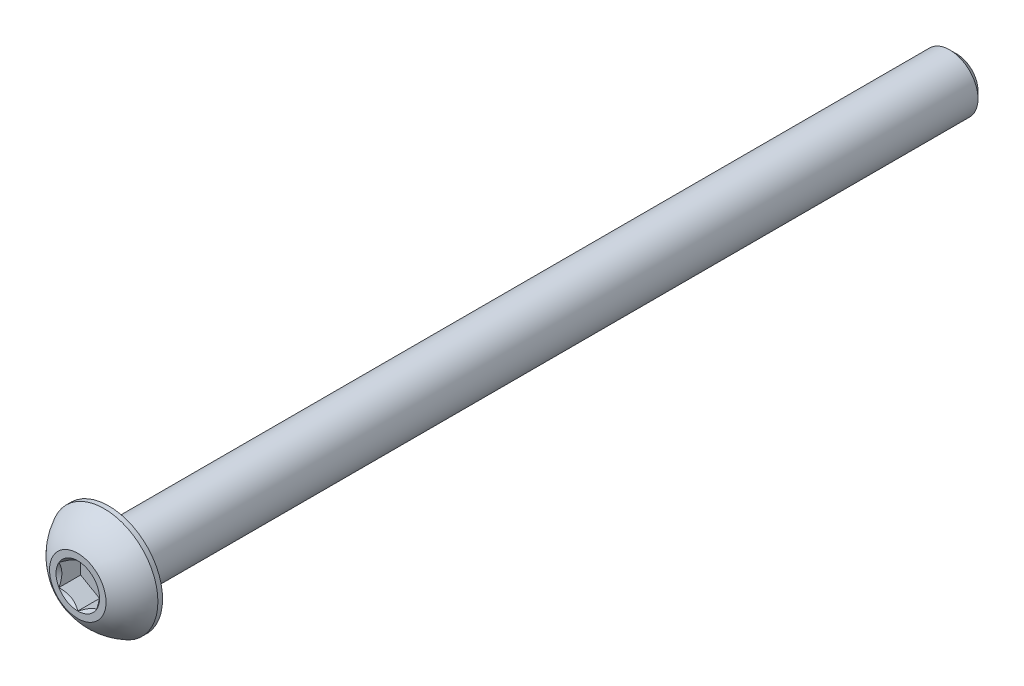
SolidWorks part; units mm, degrees
material "Chrome Stainless Steel"
ref_plane "Front" through (0, 0, 0) normal (0, 0, 1) x (1, 0, 0)
ref_plane "Top" through (0, 0, 0) normal (0, 1, 0) x (1, 0, 0)
ref_plane "Right" through (0, 0, 0) normal (1, 0, 0) x (0, 0, -1)
sketch "Sketch1" plane through (0, 0, 0) normal (1, 0, 0) x (0, 0, -1)
  line L2 (1.65, 1.5) -> (46.65, 1.5)
  line L3 (46.65, 1.5) -> (46.65, 0)
  line L4 (46.65, 0) -> (1.65, 0)
  line L6 (1.4025, 2.85) -> (1.65, 2.85) construction
  line L7 (46.65, 1.5) -> (46.65, -1.5) construction
  line L8 (0, 0) -> (1.65, 0) construction
  line L9 (1.65, 2.85) -> (1.65, -2.85) construction
  line L11 (1.65, 1.5) -> (1.65, 0)
  line L13 (0, 1) -> (0, -1) construction
  line L14 (0, 1) -> (0, 1.5) construction
  line L15 (46.6187, 1.5541) -> (46.8687, 1.1211) construction
  line L16 (46.8687, 1.1211) -> (47.1187, 1.5541) construction
  line L17 (47.1187, 1.5541) -> (46.6187, 1.5541) construction
  line L18 (46.65, 1.5) -> (47.0875, 1.5) construction
  line L19 (46.8687, 1.5541) -> (46.8687, 1.5) construction
  line L20 (46.8687, 1.5) -> (46.8687, 1.1752) construction
  line L21 (46.8687, 1.1752) -> (46.8687, 1.1211) construction
  line L22 (46.8375, 1.1752) -> (46.9, 1.1752)
  line L23 (46.6344, 1.5271) -> (47.1031, 1.5271)
  line L24 (46.9, 1.1752) -> (47.1031, 1.5271)
  line L25 (46.8375, 1.1752) -> (46.6344, 1.5271)
  line L26 (46.275, 1.5) -> (46.65, 1.125)
  arc A3 (0, 1.5) -> (1.4025, 2.85) centre (2.7948, 0) cw construction
  point P29 (46.8687, 1.5271)
  point P30 (45.4, -1.5)
  dimension "D1" = 0.2475
  dimension "Pitch" = 0.5
  dimension "D3" = 0.0625
  dimension "D2" = 0.375
  dimension "D4" = 45
  dimension "D5" = 1.25
sketch "Sketch10" plane through (0, 0, 0) normal (1, 0, 0) x (0, 0, -1)
  line L0 (46.275, 1.5) -> (46.65, 1.125) construction
  line L1 (46.275, 1.5) -> (46.65, 1.125)
  line L4 (46.65, 1.5) -> (1.65, 1.5)
  line L5 (46.65, 0) -> (46.65, 1.5)
  line L6 (1.65, 0) -> (46.65, 0)
  line L7 (1.65, 1.5) -> (1.65, 0)
  line L8 (46.275, 1.5) -> (1.65, 1.5)
  line L9 (46.65, 0) -> (46.65, 1.125)
  line L10 (1.65, 0) -> (46.65, 0)
  line L11 (1.65, 1.5) -> (1.65, 0)
  dimension "D1" = 0
revolve "Revolve3" add sketch "Sketch10" angle 360 about L8
sketch "Sketch7" plane through (0, 0, 0) normal (1, 0, 0) x (0, 0, -1)
  line L6 (1.4025, 2.85) -> (1.65, 2.85) construction
  line L8 (0, 0) -> (1.65, 0) construction
  line L11 (1.65, 2.85) -> (1.65, -2.85) construction
  line L12 (1.4025, 2.85) -> (1.65, 2.85)
  line L13 (0, 0) -> (1.65, 0)
  line L14 (0, 1) -> (0, -1) construction
  line L15 (1.65, 2.85) -> (1.65, 0)
  line L16 (0, 1.5) -> (0, 0)
  arc A2 (1.4025, 2.85) -> (0, 1.5) centre (2.7948, 0) ccw construction
  arc A3 (1.4025, 2.85) -> (0, 1.5) centre (2.7948, 0) ccw
revolve "Revolve2" add sketch "Sketch7" angle 360 mid plane about L13
sketch "Sketch5" plane through (0, 0, 0) normal (0, 0, 1) x (1, 0, 0)
  line L1 (1, -0.5774) -> (1, 0.5774)
  line L2 (1, 0.5774) -> (0, 1.1547)
  line L3 (0, 1.1547) -> (-1, 0.5774)
  line L4 (-1, 0.5774) -> (-1, -0.5774)
  line L5 (-1, -0.5774) -> (0, -1.1547)
  line L6 (0, -1.1547) -> (1, -0.5774)
  circle A0 centre (0, 0) radius 1 construction
extrude "Cut-Extrude2" cut sketch "Sketch5" against normal blind 1.155
sketch "Sketch6" plane through (0, 0, 0) normal (0, 0, 1) x (1, 0, 0)
  circle A0 centre (0, 0) radius 1.1547
extrude "Cut-Extrude3" cut sketch "Sketch6" against normal blind 1.155 draft 45
sketch "Sketch9" [suppressed] plane through (0, 0, -1.65) normal (0, 0, -1) x (-1, 0, 0)
  circle A0 centre (0, 0) radius 1.5 construction
  circle A4 centre (0, 0) radius 1.5
split "Split1" [suppressed] bodies to split 113
sketch "Sketch11" [suppressed] plane through (0, 0, -46.65) normal (0, 0, -1) x (-1, 0, 0)
  circle A0 centre (0, 0) radius 1.5 construction
  circle A1 centre (0, 0) radius 1.5
curve "Helix/Spiral1" [suppressed] pitch 0.5 height 46.65 turns 93.3
sketch "Sketch12" [suppressed] plane through (0, 0, 0) normal (1, 0, 0) x (0, 0, -1)
  line L0 (46.8375, 1.1752) -> (46.9, 1.1752) construction
  line L1 (46.9, 1.1752) -> (47.1031, 1.5271) construction
  line L2 (46.6344, 1.5271) -> (47.1031, 1.5271) construction
  line L3 (46.8375, 1.1752) -> (46.6344, 1.5271) construction
  line L4 (46.8375, 1.1752) -> (46.9, 1.1752)
  line L5 (46.9, 1.1752) -> (47.1031, 1.5271)
  line L6 (46.6344, 1.5271) -> (47.1031, 1.5271)
  line L7 (46.8375, 1.1752) -> (46.6344, 1.5271)
sweep "Cut-Sweep2" [suppressed] cut profiles "Sketch12" path "Helix/Spiral1"
extrude "Boss-Extrude1" [suppressed] add sketch "Sketch9" along normal blind 10 draft 45
equation "\"D1@Cut-Extrude2\" = \"Head Ht@Sketch1\" * .7"
equation "\"D1@Sketch1\" = \"Head Ht@Sketch1\" * .15"
equation "\"D1@Cut-Extrude3\" = \"D1@Cut-Extrude2\""
equation "\"D3@Sketch1\" = \"Pitch@Sketch1\" / 8"
equation "\"D2@Sketch1\"=\"Pitch@Sketch1\"*0.75"
equation "\"D3@Helix/Spiral1\" = \"Lg@Sketch1\" + \"Head Ht@Sketch1\""
equation "\"D4@Helix/Spiral1\"=\"pitch@sketch1\""
equation "\"D5@Sketch1\"=\"Pitch@Sketch1\"*2.5"
